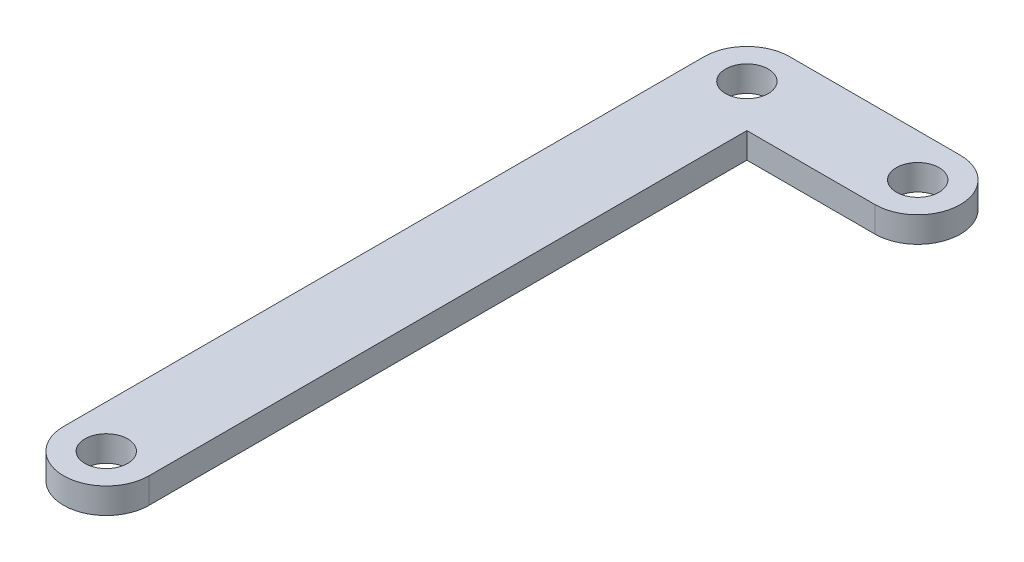
SolidWorks part; units mm, degrees
ref_plane "Front Plane" through (0, 0, 0) normal (0, 0, 1) x (1, 0, 0)
ref_plane "Top Plane" through (0, 0, 0) normal (0, 1, 0) x (1, 0, 0)
ref_plane "Right Plane" through (0, 0, 0) normal (1, 0, 0) x (0, 0, -1)
sketch "Sketch1" plane through (0, 0, 0) normal (0, 1, 0) x (1, 0, 0)
  line L7 (19.0688, -48.4258) -> (19.0688, 26.5742)
  line L8 (19.0688, 26.5742) -> (29.0688, 26.5742)
  line L9 (29.0688, -48.4258) -> (29.0688, 26.5742)
  line L10 (24.0688, 31.5742) -> (44.0688, 31.5742)
  line L11 (24.0688, 31.5742) -> (24.0688, 21.5742)
  line L12 (24.0688, 21.5742) -> (44.0688, 21.5742)
  arc A5 (19.0688, -48.4258) -> (29.0688, -48.4258) centre (24.0688, -48.4258) ccw
  circle A6 centre (24.0688, -48.4258) radius 2.5
  arc A7 (44.0688, 31.5742) -> (44.0688, 21.5742) centre (44.0688, 26.5742) cw
  circle A8 centre (44.0688, 26.5742) radius 2.5
  arc A9 (24.0688, 31.5742) -> (19.0688, 26.5742) centre (24.0688, 26.5742) ccw
  circle A10 centre (24.0688, 26.5742) radius 2.5
  point P17 (29.0688, 21.5742)
  point P24 (29.0688, 21.5742)
  dimension "D4" = 75
  dimension "D7" = 5
  dimension "D11" = 5
  dimension "D13" = 5
  dimension "D6" = 10
  dimension "D8" = 70
  dimension "D9" = 20
  dimension "D10" = 10
  dimension "D12" = 15
extrude "Boss-Extrude1" add sketch "Sketch1" along normal blind 3 contours A10 L8 L7 A5 L9 L12 L11 A6 | A10 L8 L9 L12 A7 L10 L11 A8 | A10 L11 L12 L9 L8 | A10 L11 A9 L8 region at (23.9913, 0, 13.4585) region at (21.593, 0, -29.05) region at (36.7625, 0, -26.8762) region at (26.9203, 0, -23.7227)
